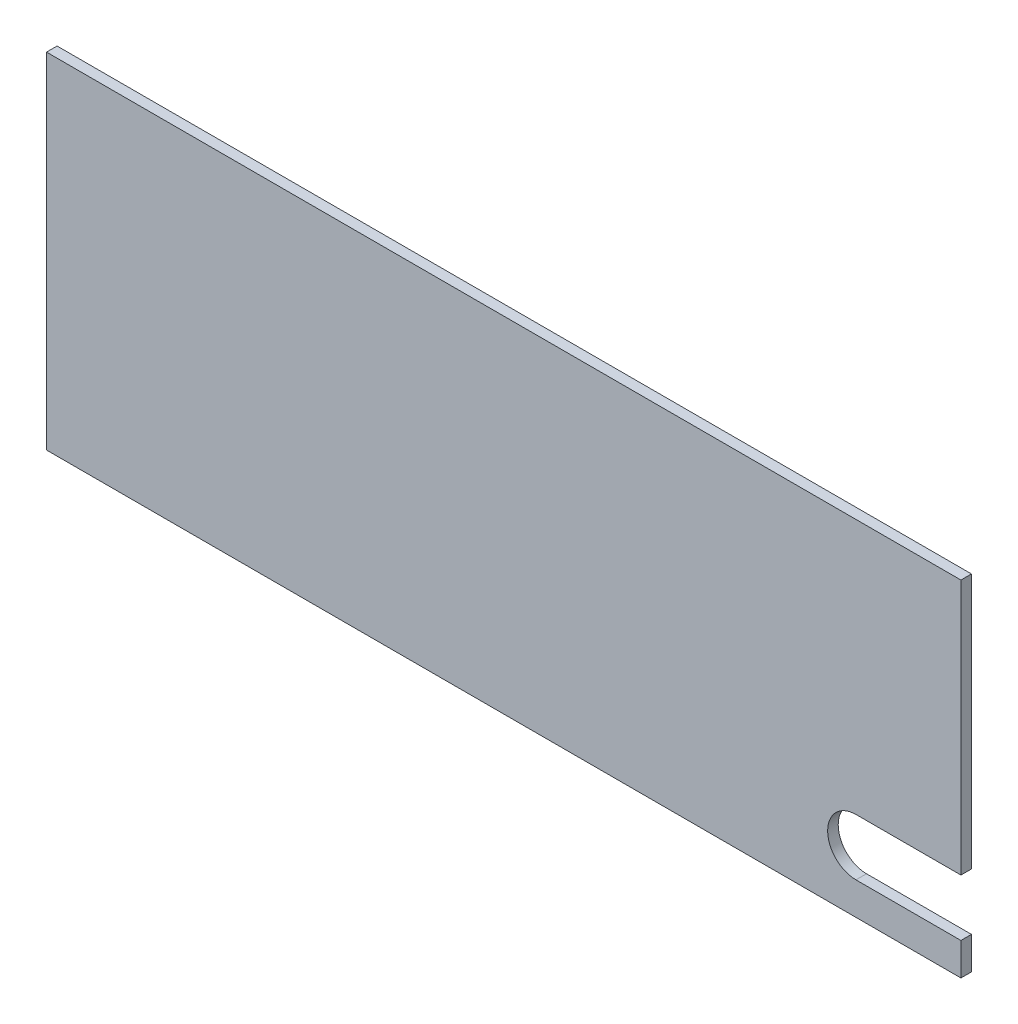
SolidWorks part; units mm, degrees
ref_plane "Piano frontale" through (0, 0, 0) normal (0, 0, 1) x (1, 0, 0)
ref_plane "Piano superiore" through (0, 0, 0) normal (0, 1, 0) x (1, 0, 0)
ref_plane "Piano destro" through (0, 0, 0) normal (1, 0, 0) x (0, 0, -1)
sketch "Schizzo1" plane through (0, 0, 0) normal (0, 0, 1) x (1, 0, 0)
  line L1 (0, 0) -> (130, 0)
  line L2 (0, 0) -> (0, 49)
  line L3 (0, 49) -> (130, 49)
  line L4 (130, 0) -> (130, 49)
  dimension "D1" = 130
  dimension "D2" = 49
extrude "Estrusione-Estrusione1" add sketch "Schizzo1" along normal blind 1.5
sketch "Schizzo2" plane through (0, 0, 1.5) normal (0, 0, 1) x (1, 0, 0)
  line L0 (144.9225, 8.6484) -> (115.0775, 8.6484) construction
  line L2 (144.9225, 4.6229) -> (115.0775, 4.6229)
  line L3 (144.9225, 12.6738) -> (115.0775, 12.6738)
  line L5 (130, 0) -> (130, 49) construction
  arc A0 (144.9225, 4.6229) -> (144.9225, 12.6738) centre (144.9225, 8.6484) ccw
  arc A1 (115.0775, 12.6738) -> (115.0775, 4.6229) centre (115.0775, 8.6484) ccw
  point P4 (130, 8.6484)
extrude "Taglio-Estrusione1" cut sketch "Schizzo2" against normal blind 12
